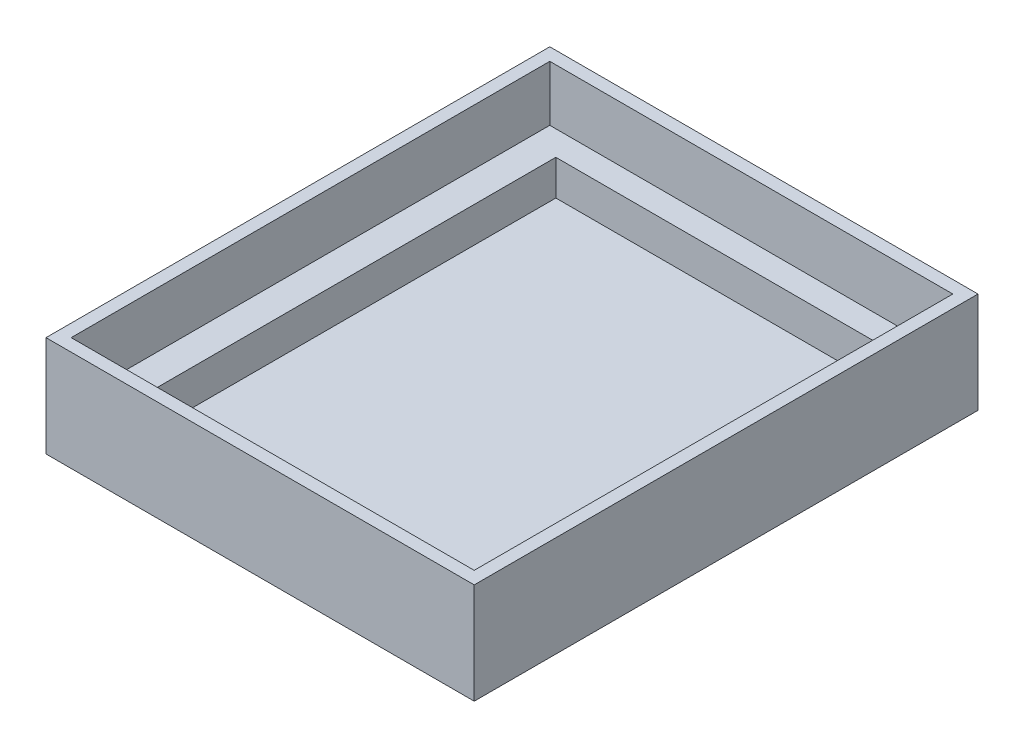
SolidWorks part; units mm, degrees
ref_plane "Front Plane" through (0, 0, 0) normal (0, 0, 1) x (1, 0, 0)
ref_plane "Top Plane" through (0, 0, 0) normal (0, 1, 0) x (1, 0, 0)
ref_plane "Right Plane" through (0, 0, 0) normal (1, 0, 0) x (0, 0, -1)
sketch "Sketch1" plane through (0, 0, 0) normal (0, 1, 0) x (1, 0, 0)
  line L1 (-40, -47.5) -> (40, -47.5)
  line L2 (-40, -47.5) -> (-40, 47.5)
  line L3 (-40, 47.5) -> (40, 47.5)
  line L4 (40, -47.5) -> (40, 47.5)
  line L5 (-40, -47.5) -> (40, 47.5) construction
  line L6 (-40, 47.5) -> (40, -47.5) construction
  point P0 (0, 0)
  dimension "D1" = 95
  dimension "D2" = 80
extrude "Boss-Extrude1" add sketch "Sketch1" along normal blind 9
sketch "Sketch2" plane through (0, 9, 0) normal (0, 1, 0) x (1, 0, 0)
  line L1 (-33.9, -42.6) -> (33.9, -42.6)
  line L2 (-33.9, -42.6) -> (-33.9, 42.6)
  line L3 (-33.9, 42.6) -> (33.9, 42.6)
  line L4 (33.9, -42.6) -> (33.9, 42.6)
  line L5 (-33.9, -42.6) -> (33.9, 42.6) construction
  line L6 (-33.9, 42.6) -> (33.9, -42.6) construction
  point P0 (0, 0)
  dimension "D1" = 85.2
  dimension "D2" = 67.8
extrude "Cut-Extrude1" cut sketch "Sketch2" against normal offset from surface (7 mm away) 2 up to face at (0, 0, 0)
sketch "Sketch3" plane through (0, 0, 0) normal (0, -1, 0) x (1, 0, 0)
  line L1 (-42.5, -50) -> (42.5, -50)
  line L2 (-42.5, -50) -> (-42.5, 50)
  line L3 (-42.5, 50) -> (42.5, 50)
  line L4 (42.5, -50) -> (42.5, 50)
  line L5 (-42.5, -50) -> (42.5, 50) construction
  line L6 (-42.5, 50) -> (42.5, -50) construction
  line L7 (-40, -47.5) -> (40, -47.5)
  line L8 (-40, -47.5) -> (-40, 47.5)
  line L9 (-40, 47.5) -> (40, 47.5)
  line L10 (40, -47.5) -> (40, 47.5)
  line L11 (-40, -47.5) -> (40, 47.5) construction
  line L12 (-40, 47.5) -> (40, -47.5) construction
  point P1 (0, 0)
  point P6 (0, 0)
  dimension "D1" = 100
  dimension "D2" = 85
extrude "Boss-Extrude2" add sketch "Sketch3" against normal blind 20
